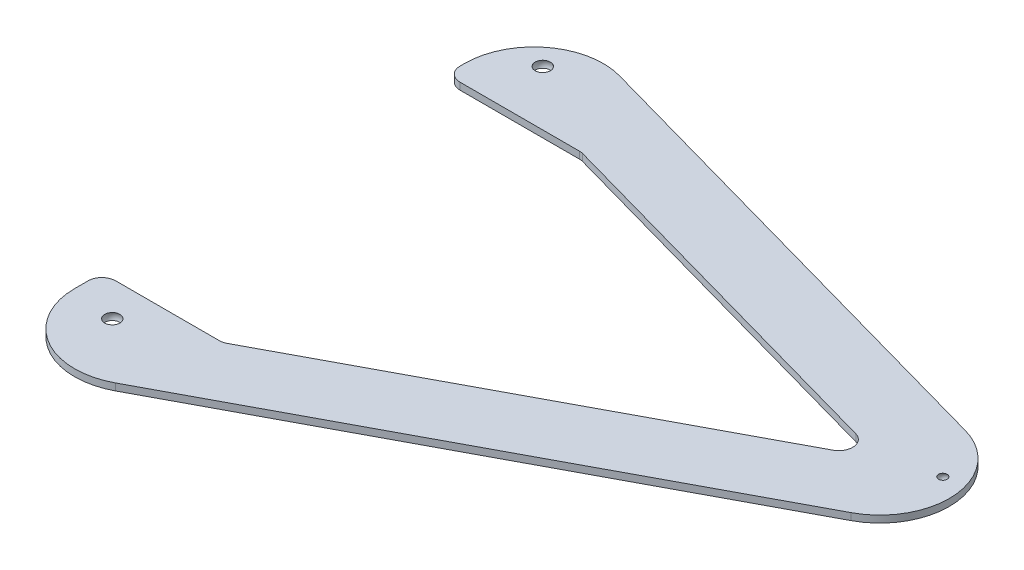
SolidWorks part; units mm, degrees
material "1060-H18"
ref_plane "Piano frontale" through (0, 0, 0) normal (0, 0, 1) x (1, 0, 0)
ref_plane "Piano superiore" through (0, 0, 0) normal (0, 1, 0) x (1, 0, 0)
ref_plane "Piano destro" through (0, 0, 0) normal (1, 0, 0) x (0, 0, -1)
sketch "Schizzo1" plane through (0, 0, 0) normal (0, 1, 0) x (1, 0, 0)
  line L0 (0, 0) -> (0, 430)
  line L1 (0, 430) -> (529.6741, 281.8605)
  line L2 (529.6741, 281.8605) -> (0, 0)
  dimension "D1" = 430
  dimension "D2" = 600
  dimension "D3" = 550
extrude "Estrusione-Estrusione1" add sketch "Schizzo1" along normal blind 5 contours L1 L2 L0
sketch "Schizzo2" plane through (0, 5, 0) normal (0, 1, 0) x (1, 0, 0)
  line L0 (0, 430) -> (529.6741, 281.8605) construction
  line L1 (0, 0) -> (0, 430) construction
  circle A0 centre (30, 390.4584) radius 2
  circle A1 centre (32.3309, 78.0684) radius 2
  circle A2 centre (430.0484, 278.5726) radius 2
  point P0 (30, 390.4584)
  point P5 (430.0484, 278.5726)
  point P6 (32.3309, 78.0684)
  dimension "D1" = 30
  dimension "D2" = 30
  dimension "D3" = 415.4
  dimension "D4" = 445.4
  dimension "D5" = 312.39
  dimension "D6" = 30
extrude "Taglio-Estrusione1" cut sketch "Schizzo2" against normal through all
fillet "Raccordo1" radius 50 2 edges at (0, 2.5, 0) (0, 2.5, -430)
sketch "Schizzo3" plane through (0, 0, 0) normal (-1, 0, 0) x (0, 0, 1)
  line L0 (-364.0973, 5) -> (-364.0973, 0) construction
  point P0 (-364.0973, 2.5)
ref_plane "Piano1" through (0, 2.5, 0) normal (0, -1, 0) x (-1, 0, 0)
sketch "Schizzo4" plane through (0, 2.5, 0) normal (0, -1, 0) x (-1, 0, 0)
  line L0 (-27.3026, 385.0989) -> (-32.6974, 395.8179)
  arc A0 (-32.6974, 395.8179) -> (-27.3026, 385.0989) centre (-30, 390.4584) cw
revolve "Rivoluzione1" add sketch "Schizzo4" angle 360 about L0
sketch "Schizzo5" plane through (0, 2.5, 0) normal (0, -1, 0) x (-1, 0, 0)
  line L0 (-431.4108, 282.3335) -> (-428.6861, 274.8118)
  arc A0 (-431.4108, 282.3335) -> (-428.6861, 274.8118) centre (-430.0484, 278.5726) ccw
revolve "Rivoluzione2" add sketch "Schizzo5" angle 360 about L0
sketch "Schizzo6" plane through (0, 2.5, 0) normal (0, -1, 0) x (-1, 0, 0)
  line L0 (-32.3309, 84.0684) -> (-32.3309, 72.0684)
  arc A0 (-32.3309, 84.0684) -> (-32.3309, 72.0684) centre (-32.3309, 78.0684) ccw
revolve "Rivoluzione3" add sketch "Schizzo6" angle 360 about L0
combine bodies "Abbina1" operation type subtract main body 102 bodies to subtract 105 104 103
fillet "Raccordo2" radius 50 1 edges at (529.6741, 2.5, -281.8605)
sketch "Schizzo7" plane through (0, 5, 0) normal (0, 1, 0) x (1, 0, 0)
  line L0 (97.4096, 350.8377) -> (395.9532, 267.3409)
  line L1 (395.9532, 267.3409) -> (86.9766, 102.9223)
  line L2 (86.9766, 102.9223) -> (-31.4393, 102.9223)
  line L3 (419.4416, 223.2014) -> (73.4884, 39.1061) construction
  line L5 (63.4672, 412.2495) -> (409.4204, 315.4931) construction
  line L6 (-31.4393, 102.9223) -> (-31.4393, 350.8377)
  line L7 (-31.4393, 350.8377) -> (97.4096, 350.8377)
  dimension "D1" = 50
  dimension "D2" = 50
  dimension "D3" = 310
  dimension "D4" = 350
extrude "Taglio-Estrusione2" cut sketch "Schizzo7" against normal through all
fillet "Raccordo3" radius 10 4 edges at (0, 2.5, -102.9223) (0, 2.5, -350.8377) (86.9766, 2.5, -102.9223) (97.4096, 2.5, -350.8377)
fillet "Raccordo4" radius 10 1 edges at (395.9532, 2.5, -267.3409)
